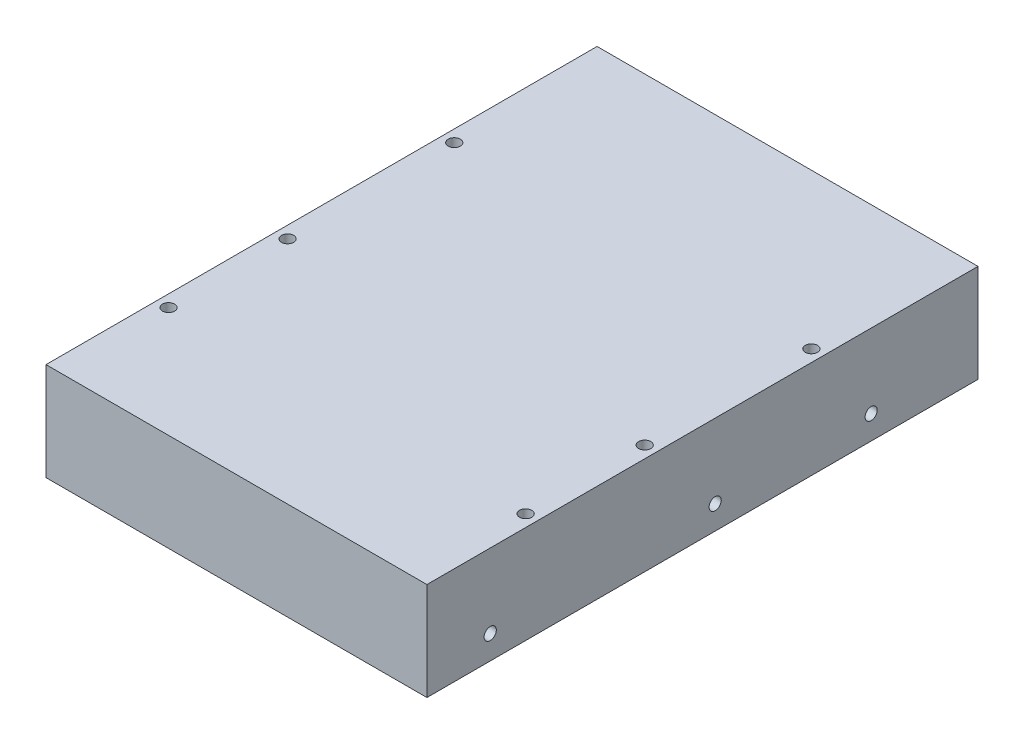
SolidWorks part; units mm, degrees
ref_plane "정면" through (0, 0, 0) normal (0, 0, 1) x (1, 0, 0)
ref_plane "윗면" through (0, 0, 0) normal (0, 1, 0) x (1, 0, 0)
ref_plane "우측면" through (0, 0, 0) normal (1, 0, 0) x (0, 0, -1)
sketch "스케치1" plane through (0, 0, 0) normal (0, 1, 0) x (1, 0, 0)
  line L0 (50.8, 146.9898) -> (50.8, 0) construction
  line L1 (0, 0) -> (101.6, 0)
  line L2 (0, 0) -> (0, 146.9898)
  line L3 (0, 146.9898) -> (101.6, 146.9898)
  line L4 (101.6, 0) -> (101.6, 146.9898)
  line L5 (3.175, 105.7148) -> (98.425, 105.7148) construction
  line L6 (3.175, 105.7148) -> (3.175, 29.5148) construction
  line L7 (3.175, 29.5148) -> (98.425, 29.5148) construction
  line L8 (98.425, 105.7148) -> (98.425, 29.5148) construction
  line L9 (3.175, 105.7148) -> (98.425, 105.7148) construction
  line L10 (3.175, 105.7148) -> (3.175, 61.2648) construction
  line L11 (3.175, 61.2648) -> (98.425, 61.2648) construction
  line L12 (98.425, 105.7148) -> (98.425, 61.2648) construction
  circle A0 centre (3.175, 105.7148) radius 1.6256
  circle A1 centre (98.425, 105.7148) radius 1.6256
  circle A2 centre (3.175, 61.2648) radius 1.6256
  circle A3 centre (98.425, 61.2648) radius 1.6256
  circle A4 centre (3.175, 29.5148) radius 1.6256
  circle A5 centre (98.425, 29.5148) radius 1.6256
  point P13 (50.8, 105.7148)
  dimension "D7" = 3.2512
  dimension "D1" = 101.6
  dimension "D2" = 146.9898
  dimension "D3" = 95.25
  dimension "D4" = 44.45
  dimension "D5" = 41.275
  dimension "D6" = 76.2
extrude "보스-돌출1" add sketch "스케치1" against normal blind 26.1112 contours L1 L4 L3 L2 A3 A2 A0 A1 A4 A5 | A1 | A3 | A5 | A4 | A2 | A0 region at (50.8, 0, -73.5217) region at (3.175, 0, -105.7148) region at (98.425, 0, -105.7148) region at (3.175, 0, -61.2648) region at (98.425, 0, -61.2648) region at (3.175, 0, -29.5148) region at (98.425, 0, -29.5148)
extrude "컷-돌출1" cut sketch "스케치1<3>" against normal blind 6.35 contours A0 | A4 | A2 | A1 | A3 | A5 region at (3.175, 0, -105.7148) region at (98.425, 0, -105.7148) region at (3.175, 0, -61.2648) region at (98.425, 0, -61.2648) region at (3.175, 0, -29.5148) region at (98.425, 0, -29.5148)
sketch "스케치1<3>" plane through (0, 0, 0) normal (0, 1, 0) x (1, 0, 0) same geometry as "스케치1"
sketch "스케치2" plane through (101.6, 0, 0) normal (1, 0, 0) x (0, 0, -1)
  line L0 (146.9898, -26.1112) -> (146.9898, 0) construction
  line L1 (0, -26.1112) -> (146.9898, -26.1112) construction
  line L2 (0, -26.1112) -> (0, -19.7612) construction
  line L3 (0, -19.7612) -> (146.9898, -19.7612) construction
  line L4 (146.9898, -26.1112) -> (146.9898, -19.7612) construction
  circle A0 centre (16.891, -19.7612) radius 1.6256
  circle A1 centre (76.8858, -19.7612) radius 1.6256
  circle A2 centre (118.491, -19.7612) radius 1.6256
  dimension "D2" = 3.2512
  dimension "D1" = 6.35
  dimension "D3" = 101.6
  dimension "D4" = 41.6052
  dimension "D5" = 28.4988
extrude "컷-돌출2" cut sketch "스케치2" against normal blind 4.7752
ref_plane "평면1" through (50.8, 0, 0) normal (1, 0, 0) x (0, 0, -1)
mirror "대칭 복사1" about plane through (50.8, 0, 0) normal (1, 0, 0) of "컷-돌출2"
